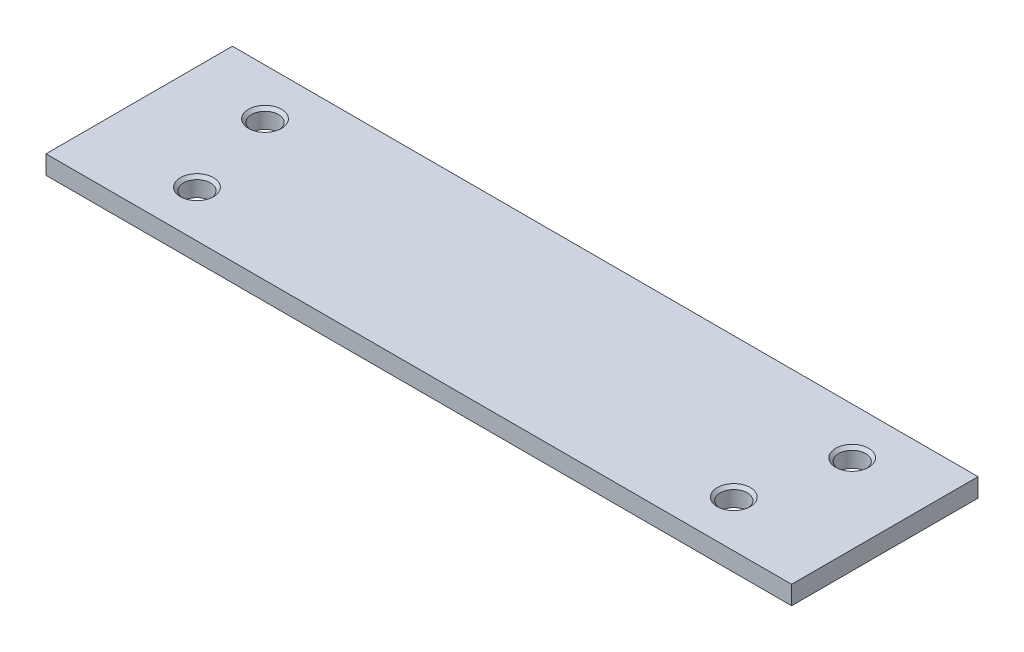
SolidWorks part; units mm, degrees
ref_plane "前视基准面" through (0, 0, 0) normal (0, 0, 1) x (1, 0, 0)
ref_plane "上视基准面" through (0, 0, 0) normal (0, 1, 0) x (1, 0, 0)
ref_plane "右视基准面" through (0, 0, 0) normal (1, 0, 0) x (0, 0, -1)
other "Configuration Table"
sketch "草图1" plane through (0, 0, 0) normal (0, 1, 0) x (1, 0, 0)
  line L0 (0, 0) -> (80, 0)
  line L2 (0, 0) -> (0, 20)
  line L3 (0, 20) -> (80, 20)
  line L4 (80, 0) -> (80, 20)
  dimension "D1" = 80
  dimension "D2" = 20
extrude "凸台-拉伸1" add sketch "草图1" along normal blind 2 contours L3 L4 L0 L2
sketch "草图2" plane through (0, 2, 0) normal (0, 1, 0) x (1, 0, 0)
  line L3 (0, 0) -> (80, 0) construction
  line L8 (0, 0) -> (0, 20) construction
  line L9 (0, 20) -> (80, 20) construction
  line L10 (80, 0) -> (80, 20) construction
  circle A0 centre (8.5, 15) radius 1
  circle A1 centre (71.5, 15) radius 1
  circle A2 centre (11.2, 5) radius 1
  circle A3 centre (68.8, 5) radius 1
  point P10 (8.5, 15)
  point P11 (71.5, 15)
  point P17 (11.2, 5)
  point P18 (68.8, 5)
  dimension "D2" = 5
  dimension "D4" = 8.5
  dimension "D1" = 2
  dimension "D10" = 2
  dimension "D11" = 2
  dimension "D3" = 2
  dimension "D5" = 5
  dimension "D6" = 8.5
  dimension "D7" = 5
  dimension "D8" = 11.2
  dimension "D9" = 5
  dimension "D12" = 11.2
sketch "草图6" plane through (0, 2, 0) normal (0, 1, 0) x (1, 0, 0)
  point P0 (8.5, 15)
  point P3 (11.2, 5)
  point P6 (71.5, 15)
  point P9 (68.8, 5)
hole_wizard "M3.5 螺纹孔1" positions "草图6" profile "草图7" tap size "M3.5" standard "GB" end condition through all
sketch "草图7" plane through (8.5, 2, -15) normal (1, 0, 0) x (0, 0, 1)
  line L0 (0, 0) -> (0, 2)
  line L1 (0, 2) -> (1.45, 2)
  line L2 (1.45, 2) -> (1.45, 0.325)
  line L3 (1.45, 0.325) -> (1.775, 0)
  line L5 (1.775, 0) -> (0, 0)
  line L6 (-1.45, 0.325) -> (-1.775, 0) construction
  line L11 (0, -6.35) -> (0, 107.95) construction
  dimension "通孔螺纹孔钻头直径" = 2.9
  dimension "通孔螺纹孔钻头深度" = 2
  dimension "近端锥形沉头孔直径" = 3.55
  dimension "近端锥形沉头孔角度" = 90
cosmetic thread "孔螺蚊线1" parameters "D1"=7, "D2"=3.5
cosmetic thread "孔螺蚊线2" parameters "D1"=7, "D2"=3.5
cosmetic thread "孔螺蚊线3" parameters "D1"=7, "D2"=3.5
cosmetic thread "孔螺蚊线4" parameters "D1"=7, "D2"=3.5
